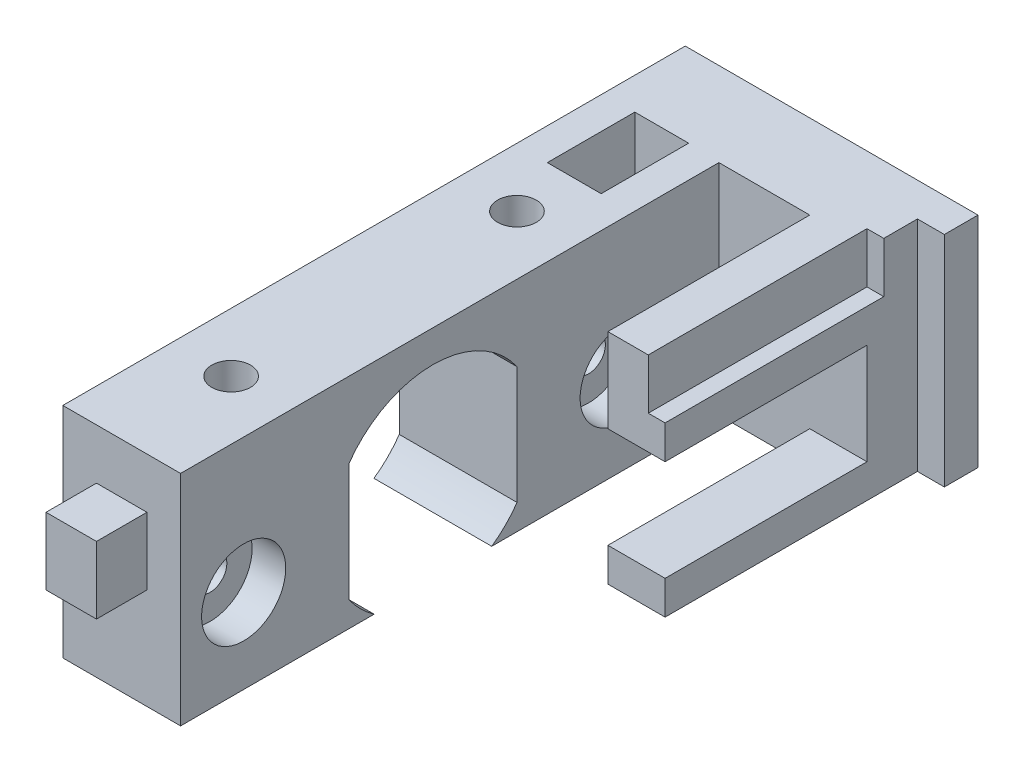
SolidWorks part; units mm, degrees
ref_plane "Front Plane" through (0, 0, 0) normal (0, 0, 1) x (1, 0, 0)
ref_plane "Top Plane" through (0, 0, 0) normal (0, 1, 0) x (1, 0, 0)
ref_plane "Right Plane" through (0, 0, 0) normal (1, 0, 0) x (0, 0, -1)
sketch "Sketch2" plane through (0, 0, 0) normal (1, 0, 0) x (0, 0, -1)
  line L0 (-11.25, 0) -> (11.25, 0) construction
  line L5 (3.4943, -5) -> (15, -5)
  line L7 (-15, -5) -> (-3.4943, -5)
  line L8 (-15, -5) -> (-15, 8)
  line L9 (-15, 8) -> (15, 8)
  line L10 (15, -5) -> (15, 8)
  line L11 (-21.1921, -10.5) -> (21.1921, -10.5)
  line L12 (-26.7679, -7) -> (23.2321, -7) construction
  line L13 (-26.7679, -7) -> (-26.7679, -5) construction
  line L14 (-26.7679, -5) -> (-3.4943, -5) construction
  line L15 (23.2321, -7) -> (23.2321, -5) construction
  line L16 (-26.7679, -7) -> (23.2321, -5) construction
  line L17 (-26.7679, -5) -> (23.2321, -7) construction
  line L18 (-5, -3.4943) -> (-5, 3.4943)
  line L19 (8.75, -3) -> (13.75, -3) construction
  line L20 (8.75, -3) -> (8.75, 3) construction
  line L21 (8.75, 3) -> (13.75, 3) construction
  line L22 (13.75, -3) -> (13.75, 3) construction
  line L23 (8.75, -3) -> (13.75, 3) construction
  line L24 (8.75, 3) -> (13.75, -3) construction
  line L26 (5, -3.4943) -> (5, 3.4943)
  line L27 (-5, -3.4943) -> (5, 3.4943) construction
  line L28 (-5, 3.4943) -> (5, -3.4943) construction
  line L29 (3.4943, -5) -> (23.2321, -5) construction
  circle A2 centre (0, 0) radius 1.75 construction
  circle A3 centre (11.25, 0) radius 9.5 construction
  circle A4 centre (-11.25, 0) radius 9.5 construction
  circle A5 centre (11.25, 0) radius 10.5 construction
  circle A6 centre (-11.25, 0) radius 10.5 construction
  circle A7 centre (0, 0) radius 0.5
  circle A8 centre (-11.25, 0) radius 1
  circle A9 centre (11.25, 0) radius 1
  arc A10 (5, 3.4943) -> (-5, 3.4943) centre (0, 0) ccw
  arc A11 (-5, -3.4943) -> (-3.4943, -5) centre (0, 0) ccw
  arc A13 (3.4943, -5) -> (5, -3.4943) centre (0, 0) ccw
  point P14 (0, 0)
  point P18 (0, 8)
  point P19 (-1.7679, -6)
  point P30 (0, -10.5)
  dimension "D3" = 3.5
  dimension "D4" = 19
  dimension "D5" = 21
  dimension "D6" = 30
  dimension "D10" = 1
  dimension "D11" = 2
  dimension "D2" = 12.2
  dimension "D7" = 13
  dimension "D8" = 2
  dimension "D9" = 50
  dimension "D12" = 5
  dimension "D13" = 6
  dimension "D14" = 10
extrude "Boss-Extrude1" add sketch "Sketch2" along normal blind 7 contours L7 L10 L9 L8 A9 A8 region at (0, -4.5445, -4.5445)
sketch "Sketch3" plane through (0, 0, 0) normal (0, 1, 0) x (1, 0, 0)
  line L0 (0, 3.4943) -> (0, 15) construction
  line L1 (7, 3.4943) -> (0, 3.4943) construction
  line L2 (7, -3.4943) -> (0, -3.4943) construction
  circle A0 centre (3.5, 8.4943) radius 1.15
  circle A1 centre (3.5, -8.4943) radius 1.15
  dimension "D1" = 2.3
  dimension "D2" = 3.5
  dimension "D3" = 5
  dimension "D4" = 5
extrude "Cut-Extrude1" cut sketch "Sketch3" along normal blind 13 from surface starting at face at (3.5, -5, -9.2471)
sketch "Sketch5" plane through (0, 0, 0) normal (1, 0, 0) x (0, 0, -1)
  circle A0 centre (11.25, 0) radius 2.5
  circle A1 centre (-11.25, 0) radius 2.5
  dimension "D1" = 5
extrude "Cut-Extrude2" cut sketch "Sketch5" along normal blind 2
extrude "Cut-Extrude3" cut sketch "Sketch5<2>" against normal blind 2 from surface starting at face at (7, -0.1527, 0)
sketch "Sketch5<2>" plane through (0, 0, 0) normal (1, 0, 0) x (0, 0, -1) same geometry as "Sketch5"
sketch "Sketch6" plane through (0, 0, 0) normal (0, 1, 0) x (1, 0, 0)
  line L0 (0, 15) -> (7, 15)
  line L2 (0, 15) -> (0, 25)
  line L3 (0, 25) -> (17.4, 25)
  line L6 (17.4, 25) -> (17.4, 5)
  line L7 (17.4, 5) -> (12.4, 5)
  line L8 (12.4, 22) -> (12.4, 5)
  line L9 (7, 15) -> (7, 22)
  line L10 (7, 22) -> (12.4, 22)
  dimension "D1" = 10
  dimension "D2" = 10.4
  dimension "D3" = 20
  dimension "D4" = 3
  dimension "D5" = 5
extrude "Boss-Extrude2" add sketch "Sketch6" along normal up to surface (8 mm away) from surface up to face at (3.5, 8, -7.3443) starting at face at (3.5, -5, -7.3443)
sketch "Sketch7" plane through (0, 0, 0) normal (1, 0, 0) x (0, 0, -1)
  line L0 (5, 8) -> (5, -5) construction
  line L1 (5, -3) -> (17, -3)
  line L2 (5, -3) -> (5, 3)
  line L3 (5, 3) -> (17, 3)
  line L4 (17, -3) -> (17, 3)
  line L5 (5, -5) -> (25, -5) construction
  dimension "D1" = 6
  dimension "D2" = 2
  dimension "D3" = 12
extrude "Cut-Extrude4" cut sketch "Sketch7" against normal blind 6 from surface starting at face at (17.4, 1.5, -15)
sketch "Sketch8" plane through (0, 0, 0) normal (1, 0, 0) x (0, 0, -1)
  line L0 (5, 8) -> (25, 8) construction
  line L1 (5, -5) -> (20, -5)
  line L2 (5, -5) -> (5, 8)
  line L3 (5, 8) -> (20, 8)
  line L4 (20, -5) -> (20, 8)
  dimension "D1" = 15
extrude "Cut-Extrude5" cut sketch "Sketch8" against normal blind 1.6 from surface starting at face at (17.4, 0.75, -13)
sketch "Sketch9" plane through (0, 0, 0) normal (1, 0, 0) x (0, 0, -1)
  line L1 (5, 8) -> (18, 8)
  line L2 (5, 8) -> (5, 5)
  line L3 (5, 5) -> (18, 5)
  line L4 (18, 8) -> (18, 5)
  dimension "D1" = 13
  dimension "D2" = 3
extrude "Cut-Extrude6" cut sketch "Sketch9" against normal blind 1 from surface starting at face at (15.8, 0.75, -11.75)
sketch "Sketch10" plane through (0, 0, 0) normal (0, 1, 0) x (1, 0, 0)
  line L0 (12.4, 22) -> (12.4, 5) construction
  line L1 (7, 22) -> (12.4, 22)
  line L2 (7, 22) -> (7, 17)
  line L3 (7, 17) -> (12.4, 17)
  line L4 (12.4, 22) -> (12.4, 17)
  dimension "D1" = 5
extrude "Boss-Extrude3" add sketch "Sketch10" against normal up to surface (5 mm away) from surface up to face at (3.5, -5, -7.3443) starting at face at (3.5, 8, -7.3443)
sketch "Sketch11" plane through (0, 0, 0) normal (0, 1, 0) x (1, 0, 0)
  line L0 (0, -15) -> (0, 25) construction
  line L1 (17.4, 25) -> (0, 25)
  line L2 (17.4, 25) -> (17.4, 22)
  line L3 (17.4, 22) -> (0, 22)
  line L4 (0, 25) -> (0, 22)
  dimension "D1" = 3
extrude "Cut-Extrude7" cut sketch "Sketch11" against normal up to surface (5 mm away) from surface up to face at (10.52, -5, -14.0989) starting at face at (3.5, 8, -7.3443)
sketch "Sketch12" plane through (0, 0, 0) normal (0, 0, 1) x (1, 0, 0)
  line L0 (7, -5) -> (0, -5) construction
  line L1 (2, 5) -> (5, 5)
  line L2 (2, 5) -> (2, 1)
  line L3 (2, 1) -> (5, 1)
  line L4 (5, 5) -> (5, 1)
  line L5 (2, 5) -> (5, 1) construction
  line L6 (2, 1) -> (5, 5) construction
  line L7 (0, -5) -> (0, 8) construction
  point P0 (3.5, 3)
  dimension "D1" = 3
  dimension "D2" = 4
  dimension "D3" = 6
  dimension "D4" = 2
extrude "Boss-Extrude4" add sketch "Sketch12" along normal blind 3 from surface starting at face at (3.5, 1.5, 15)
sketch "Sketch13" plane through (0, 0, 0) normal (0, 1, 0) x (1, 0, 0)
  line L0 (17.4, 22) -> (0, 22) construction
  line L1 (1.9, 17.1) -> (5.1, 17.1)
  line L2 (1.9, 17.1) -> (1.9, 11.9)
  line L3 (1.9, 11.9) -> (5.1, 11.9)
  line L4 (5.1, 17.1) -> (5.1, 11.9)
  line L5 (1.9, 17.1) -> (5.1, 11.9) construction
  line L6 (1.9, 11.9) -> (5.1, 17.1) construction
  line L7 (7, -15) -> (7, 17) construction
  point P0 (3.5, 14.5)
  dimension "D1" = 5.2
  dimension "D2" = 3.2
  dimension "D3" = 4.9
  dimension "D4" = 1.9
extrude "Cut-Extrude8" cut sketch "Sketch13" against normal blind 3.2 from surface starting at face at (3.5, 8, -7.3443)
